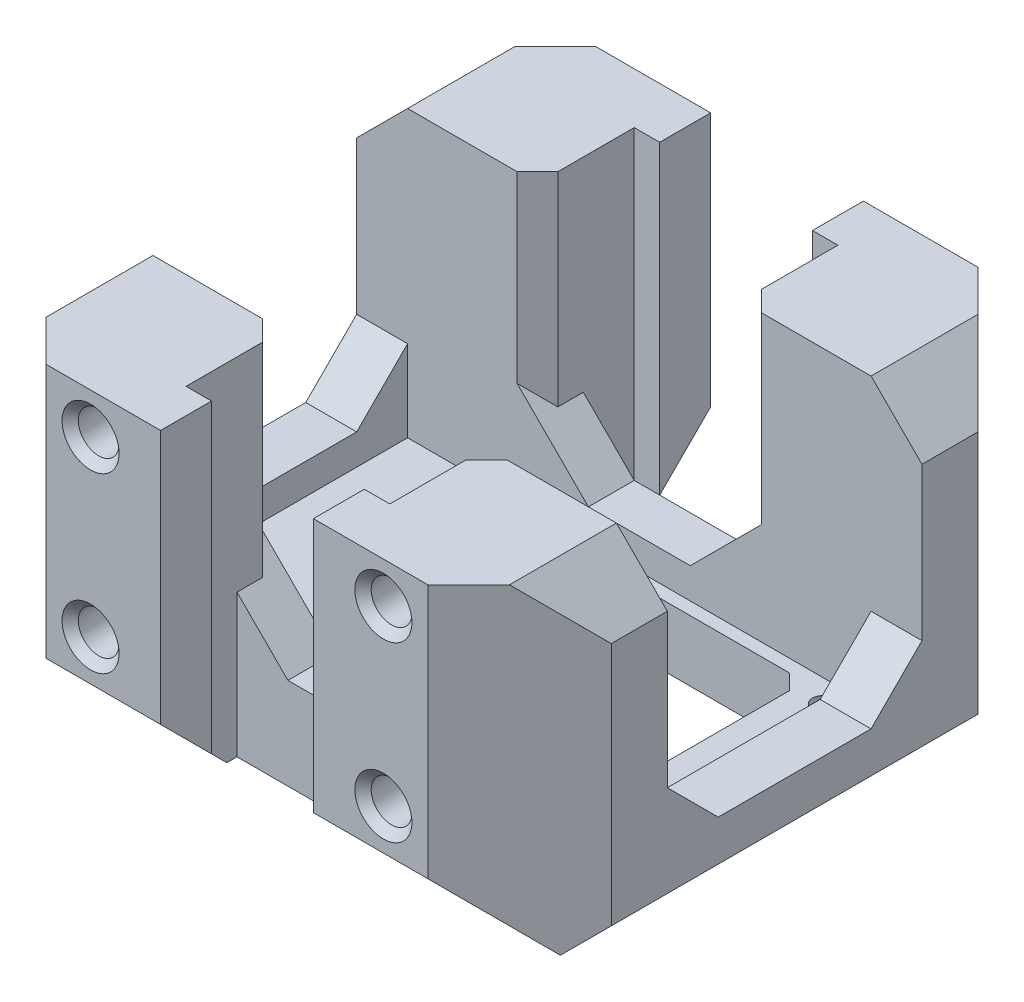
SolidWorks part; units mm, degrees
ref_plane "Front Plane" through (0, 0, 0) normal (0, 0, 1) x (1, 0, 0)
ref_plane "Top Plane" through (0, 0, 0) normal (0, 1, 0) x (1, 0, 0)
ref_plane "Right Plane" through (0, 0, 0) normal (1, 0, 0) x (0, 0, -1)
sketch "Sketch1" plane through (0, 0, 0) normal (0, 1, 0) x (1, 0, 0)
  line L0 (-27.75, -17.5) -> (-27.75, 17.5)
  line L1 (-22.75, -12.5) -> (22.75, -12.5)
  line L2 (-22.75, -12.5) -> (-22.75, 12.5)
  line L3 (-22.75, 12.5) -> (22.75, 12.5)
  line L4 (22.75, -12.5) -> (22.75, 12.5)
  line L5 (-22.75, -12.5) -> (22.75, 12.5) construction
  line L6 (-22.75, 12.5) -> (22.75, -12.5) construction
  line L7 (-27.75, 17.5) -> (27.75, 17.5)
  line L8 (27.75, -17.5) -> (27.75, 17.5)
  line L9 (-27.75, -17.5) -> (27.75, -17.5)
  point P0 (0, 0)
  dimension "D1" = 45.5
  dimension "D2" = 25
  dimension "D3" = 5
extrude "Boss-Extrude1" add sketch "Sketch1" along normal blind 28
sketch "Sketch2" plane through (0, 0, 0) normal (0, -1, 0) x (1, 0, 0)
  line L0 (-27.75, 17.5) -> (27.75, 17.5) construction
  line L1 (-27.75, 17.5) -> (27.75, 17.5)
  line L2 (-27.75, -17.5) -> (-27.75, 17.5) construction
  line L3 (27.75, -17.5) -> (-27.75, -17.5) construction
  line L4 (27.75, 17.5) -> (27.75, -17.5) construction
  line L5 (-27.75, -17.5) -> (-27.75, 17.5)
  line L6 (27.75, -17.5) -> (-27.75, -17.5)
  line L7 (27.75, 17.5) -> (27.75, -17.5)
extrude "Boss-Extrude2" add sketch "Sketch2" along normal blind 6
sketch "Sketch4" plane through (0, 0, 0) normal (0, 1, 0) x (1, 0, 0)
  line L0 (22.75, -12.5) -> (22.75, 12.5) construction
  line L1 (-4.2, -10.25) -> (20.25, -10.25) construction
  line L2 (-4.2, -10.25) -> (-4.2, 10.25) construction
  line L3 (-4.2, 10.25) -> (20.25, 10.25) construction
  line L4 (20.25, -10.25) -> (20.25, 10.25) construction
  line L5 (-4.2, -10.25) -> (20.25, 10.25) construction
  line L6 (-4.2, 10.25) -> (20.25, -10.25) construction
  circle A0 centre (-4.2, 10.25) radius 1
  circle A1 centre (20.25, 10.25) radius 1
  circle A2 centre (20.25, -10.25) radius 1
  circle A3 centre (-4.2, -10.25) radius 1
  point P0 (8.025, 0)
  dimension "D1" = 2
  dimension "D2" = 20.5
  dimension "D3" = 24.45
  dimension "D4" = 2.5
extrude "Cut-Extrude1" cut sketch "Sketch4" against normal blind 3.5
sketch "Sketch5" plane through (0, -3.5, 0) normal (0, 1, 0) x (1, 0, 0)
  circle A0 centre (-4.2, 10.25) radius 2
  circle A1 centre (20.25, 10.25) radius 2
  circle A2 centre (20.25, -10.25) radius 2
  circle A3 centre (-4.2, -10.25) radius 2
  dimension "D1" = 4
extrude "Cut-Extrude2" cut sketch "Sketch5" against normal up to next
sketch "Sketch6" plane through (0, 0, 0) normal (0, 1, 0) x (1, 0, 0)
  line L1 (-1.75, -11.25) -> (17.5, -11.25)
  line L2 (-1.75, -11.25) -> (-1.75, 11.25)
  line L3 (-1.75, 11.25) -> (17.5, 11.25)
  line L4 (17.5, -11.25) -> (17.5, 11.25)
  line L5 (-1.75, -11.25) -> (17.5, 11.25) construction
  line L6 (-1.75, 11.25) -> (17.5, -11.25) construction
  circle A0 centre (20.25, 10.25) radius 1 construction
  point P0 (7.875, 0)
  dimension "D1" = 22.5
  dimension "D2" = 19.25
  dimension "D3" = 2.75
extrude "Cut-Extrude3" cut sketch "Sketch6" against normal up to next
chamfer "Chamfer1" distance 1.5 angle 45 4 edges at (-1.75, -3, 11.25) (17.5, -3, 11.25) (-1.75, -3, -11.25) (17.5, -3, -11.25)
sketch "Sketch7" plane through (0, 0, 0) normal (0, 1, 0) x (1, 0, 0)
  line L0 (-1.75, 9.75) -> (-1.75, -9.75) construction
  circle A0 centre (-12.5, 0) radius 3
  dimension "D1" = 6
  dimension "D2" = 10.75
extrude "Cut-Extrude4" cut sketch "Sketch7" against normal up to next
chamfer "Chamfer2" distance 1 angle 45 2 edges at (-12.5, -6, 3) (-12.5, 0, 3)
sketch "Sketch8" plane through (0, 28, 0) normal (0, 1, 0) x (1, 0, 0)
  line L6 (27.75, -17.5) -> (27.75, 17.5) construction
  line L7 (-27.75, -17.5) -> (27.75, -17.5)
  line L8 (-27.75, -17.5) -> (-27.75, -27)
  line L9 (-27.75, -27) -> (27.75, -27)
  line L10 (27.75, -17.5) -> (27.75, -27)
  dimension "D1" = 9.5
extrude "Boss-Extrude3" add sketch "Sketch8" against normal up to surface (34 mm away) up to face at (-12.5, -6, 4)
sketch "Sketch10" plane through (0, 28, 0) normal (0, 1, 0) x (1, 0, 0)
  line L0 (-27.75, -27) -> (27.75, -27) construction
  line L1 (-10, -17) -> (10, -17)
  line L2 (-10, -17) -> (-10, -22)
  line L3 (-10, -22) -> (10, -22)
  line L4 (10, -17) -> (10, -22)
  line L5 (-10, -17) -> (10, -22) construction
  line L6 (-10, -22) -> (10, -17) construction
  line L7 (-7.5, -27) -> (7.5, -27)
  line L8 (-7.5, -27) -> (-7.5, -22)
  line L9 (-7.5, -22) -> (7.5, -22)
  line L10 (7.5, -27) -> (7.5, -22)
  line L11 (-7.5, -27) -> (7.5, -22) construction
  line L12 (-7.5, -22) -> (7.5, -27) construction
  point P0 (0, -19.5)
  point P5 (0, -24.5)
  point P15 (-7.5, -24.5)
  line M10 (-27.75, -27) -> (27.75, -27)
  dimension "D1" = 5
  dimension "D2" = 20
  dimension "D3" = 15
extrude "Cut-Extrude5" cut sketch "Sketch10" against normal up to next contours L4 L1 L2 L3 | L10 L3 L8 M10 region at (0, 28, 19.5) region at (0, 28, 24.5)
mirror "Mirror3" about plane through (0, 0, 0) normal (0, 0, 1) of "Cut-Extrude5", "Boss-Extrude3"
chamfer "Chamfer7" distance 9 angle 45 8 edges at (17.625, -6, -27) (27.75, 11, -27) (-17.625, -6, -27) (-27.75, 11, -27) (17.625, -6, 27) (27.75, 11, 27) (-17.625, -6, 27) (-27.75, 11, 27)
chamfer "Chamfer8" distance 5 angle 45 2 edges at (27.75, 28, 0) (-27.75, 28, 0)
chamfer "Chamfer9" distance 5 angle 45 2 edges at (27.75, -6, 0) (-27.75, -6, 0)
sketch "Sketch12" plane through (0, 0, -27) normal (0, 0, -1) x (-1, 0, 0)
  line L0 (18.75, 28) -> (7.5, 28) construction
  line L1 (-14.375, 7) -> (14.375, 7) construction
  line L2 (-14.375, 7) -> (-14.375, 24) construction
  line L3 (-14.375, 24) -> (14.375, 24) construction
  line L4 (14.375, 7) -> (14.375, 24) construction
  line L5 (-14.375, 7) -> (14.375, 24) construction
  line L6 (-14.375, 24) -> (14.375, 7) construction
  line L7 (7.5, 3) -> (18.75, 3) construction
  circle A0 centre (-14.375, 24) radius 1.45
  circle A1 centre (14.375, 24) radius 1.45
  circle A2 centre (14.375, 7) radius 1.45
  circle A3 centre (-14.375, 7) radius 1.45
  point P0 (0, 15.5)
  dimension "D1" = 2.9
  dimension "D3" = 4
  dimension "D4" = 4
  dimension "D2" = 28.75
extrude "Cut-Extrude7" cut sketch "Sketch12" against normal blind 10
mirror "Mirror4" about plane through (0, 0, 0) normal (0, 0, 1) of "Cut-Extrude7"
sketch "Sketch13" plane through (0, 0, -12.5) normal (0, 0, 1) x (1, 0, 0)
  line L0 (10, -6) -> (10, 28) construction
  line L1 (-10, 28) -> (10, 28)
  line L2 (-10, 28) -> (-10, 3)
  line L3 (-10, 3) -> (10, 3)
  line L4 (10, 28) -> (10, 3)
  line L6 (18.75, 3) -> (7.5, 3) construction
extrude "Cut-Extrude8" cut sketch "Sketch13" against normal up to next
sketch "Sketch14" plane through (22.75, 0, 0) normal (-1, 0, 0) x (0, 0, 1)
  line L0 (12.5, 28) -> (12.5, 0) construction
  line L1 (-12.5, 28) -> (12.5, 28)
  line L2 (-12.5, 28) -> (-12.5, 3)
  line L3 (-12.5, 3) -> (12.5, 3)
  line L4 (12.5, 28) -> (12.5, 3)
  line L5 (-17, 3) -> (-12.5, 3) construction
extrude "Cut-Extrude9" cut sketch "Sketch14" against normal up to next
mirror "Mirror5" about plane through (0, 0, 0) normal (1, 0, 0) of "Cut-Extrude9"
mirror "Mirror6" about plane through (0, 0, 0) normal (0, 0, 1) of "Cut-Extrude8"
chamfer "Chamfer10" distance 5 angle 45 8 edges at (-25.25, 3, 12.5) (-25.25, 3, -12.5) (-10, 3, 14.75) (10, 3, 14.75) (25.25, 3, 12.5) (25.25, 3, -12.5) (-10, 3, -14.75) (10, 3, -14.75)
chamfer "Chamfer11" distance 2 angle 45 4 edges at (10, 18, -12.5) (-10, 18, 12.5) (-10, 18, -12.5) (10, 18, 12.5)
sketch "Sketch15" plane through (0, 0, -27) normal (0, 0, -1) x (-1, 0, 0)
  circle A0 centre (-14.375, 24) radius 2
  circle A1 centre (14.375, 24) radius 2
  circle A2 centre (14.375, 7) radius 2
  circle A3 centre (-14.375, 7) radius 2
  dimension "D1" = 4
extrude "Cut-Extrude10" cut sketch "Sketch15" against normal blind 5.2
mirror "Mirror7" about plane through (0, 0, 0) normal (0, 0, 1) of "Cut-Extrude10"
chamfer "Chamfer12" distance 0.8 angle 45 8 edges at (12.375, 7, 27) (12.375, 24, 27) (-16.375, 7, 27) (-16.375, 24, 27) (12.375, 7, -27) (12.375, 24, -27) (-16.375, 7, -27) (-16.375, 24, -27)
